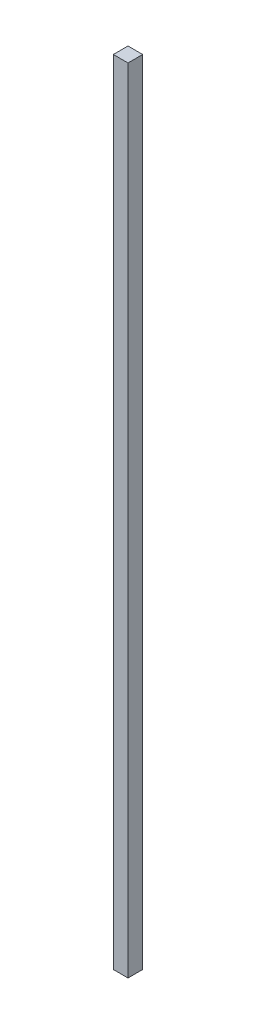
SolidWorks part; units mm, degrees
ref_plane "Ebene vorne" through (0, 0, 0) normal (0, 0, 1) x (1, 0, 0)
ref_plane "Ebene oben" through (0, 0, 0) normal (0, 1, 0) x (1, 0, 0)
ref_plane "Ebene rechts" through (0, 0, 0) normal (1, 0, 0) x (0, 0, -1)
sketch "Skizze1" plane through (0, 0, 0) normal (0, 1, 0) x (1, 0, 0)
  line L1 (0, 0) -> (50, 0)
  line L2 (0, 0) -> (0, 50)
  line L3 (0, 50) -> (50, 50)
  line L4 (50, 0) -> (50, 50)
  dimension "D1" = 50
  dimension "D2" = 50
extrude "Aufsatz-Linear austragen1" add sketch "Skizze1" along normal blind 2700
